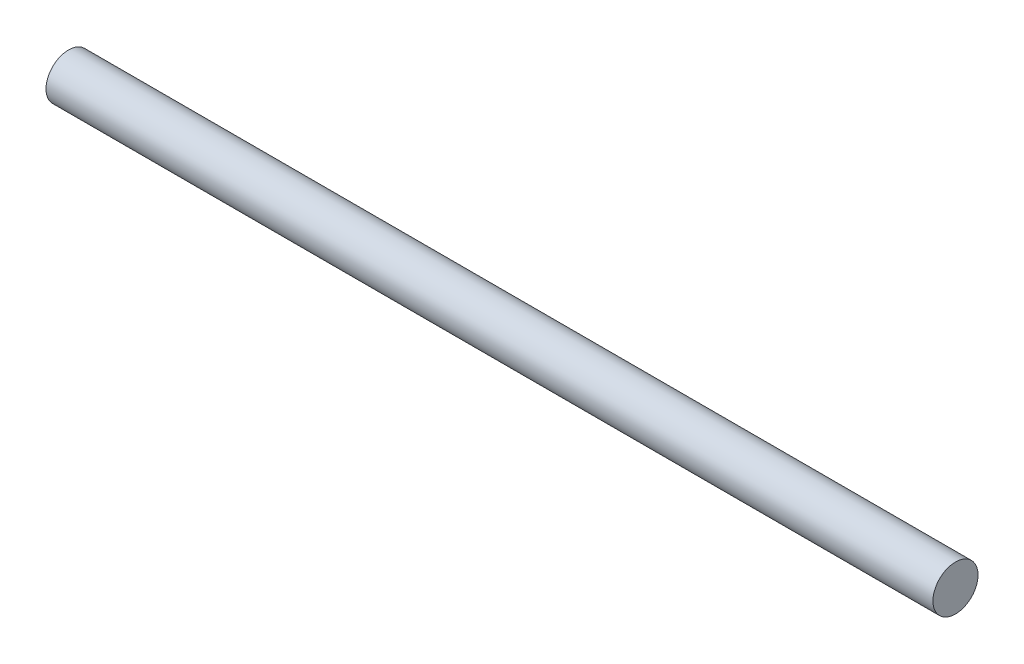
SolidWorks part; units mm, degrees
ref_plane "Alzado" through (0, 0, 0) normal (0, 0, 1) x (1, 0, 0)
ref_plane "Planta" through (0, 0, 0) normal (0, 1, 0) x (1, 0, 0)
ref_plane "Vista lateral" through (0, 0, 0) normal (1, 0, 0) x (0, 0, -1)
sketch "Croquis1" plane through (0, 0, 0) normal (1, 0, 0) x (0, 0, -1)
  circle A0 centre (0, 0) radius 4.7625
  dimension "D1" = 9.525
extrude "Saliente-Extruir1" add sketch "Croquis1" along normal blind 187.24
